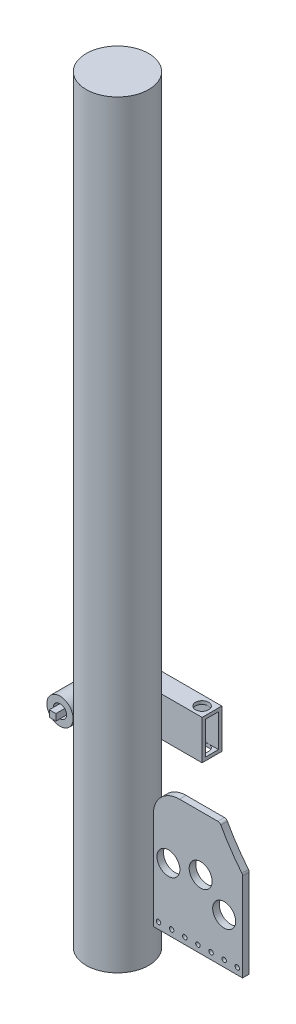
SolidWorks part; units mm, degrees
ref_plane "Front Plane" through (0, 0, 0) normal (0, 0, 1) x (1, 0, 0)
ref_plane "Top Plane" through (0, 0, 0) normal (0, 1, 0) x (1, 0, 0)
ref_plane "Right Plane" through (0, 0, 0) normal (1, 0, 0) x (0, 0, -1)
sketch "Elevation Bar" plane through (0, 0, 0) normal (0, 1, 0) x (1, 0, 0)
  circle A0 centre (0, 0) radius 30.226
  dimension "D1" = 60.452
extrude "Elevation Bar Part" add sketch "Elevation Bar" along normal blind 734.06
sketch "Pole and Drivetrain Pos" plane through (0, 0, 0) normal (0, 0, 1) x (1, 0, 0)
  line L0 (0, 0) -> (172.1794, 0) construction
  line L1 (-30.226, 0) -> (-30.226, 734.06) construction
  line L2 (-30.226, 734.06) -> (30.226, 734.06) construction
  line L3 (30.226, 734.06) -> (30.226, 0) construction
  line L4 (30.226, 0) -> (30.226, 734.06) construction
  line L5 (636.651, 41.275) -> (27.051, 41.275) construction
  line L6 (636.651, 53.975) -> (27.051, 53.975)
  line L7 (636.651, 53.975) -> (636.651, 28.575)
  line L8 (636.651, 28.575) -> (27.051, 28.575)
  line L9 (27.051, 53.975) -> (27.051, 28.575)
  line L10 (-30.226, 93.98) -> (30.226, 93.98) construction
  line L11 (33.2486, 0) -> (-33.2486, 0) construction
  line L12 (30.226, 185.42) -> (-30.226, 185.42) construction
  line L13 (30.226, 276.86) -> (-30.226, 276.86) construction
  line L14 (30.226, 368.3) -> (-30.226, 368.3) construction
  line L15 (30.226, 459.74) -> (-30.226, 459.74) construction
  line L16 (30.226, 551.18) -> (-30.226, 551.18) construction
  line L17 (30.226, 642.62) -> (-30.226, 642.62) construction
  line L18 (30.226, 73.152) -> (750.8896, 73.152) construction
  circle A0 centre (579.501, 41.275) radius 41.275 construction
  circle A1 centre (84.201, 41.275) radius 41.275 construction
  circle A2 centre (331.851, 41.275) radius 41.275 construction
  circle A3 centre (84.201, 41.275) radius 25.4
  point P24 (331.851, 41.275)
  dimension "D2" = 82.55
  dimension "D5" = 50.8
  dimension "D1" = 609.6
  dimension "D3" = 25.4
  dimension "D6" = 93.98
  dimension "D7" = 185.42
  dimension "D8" = 276.86
  dimension "D9" = 368.3
  dimension "D10" = 459.74
  dimension "D11" = 551.18
  dimension "D12" = 642.62
  dimension "D13" = 73.152
  dimension "D14" = 57.15
  dimension "D4" = 57.15
  dimension "D15" = 6.35
sketch "Driving Wheels Geo" plane through (0, 0, 0) normal (0, 0, 1) x (1, 0, 0)
  line L0 (-30.226, 182.88) -> (-30.226, 101.727) construction
  line L1 (55.626, 101.727) -> (30.226, 101.727) construction
  line L2 (-30.226, 0) -> (-30.226, 734.06) construction
  line L3 (30.226, 734.06) -> (30.226, 0) construction
  line L5 (30.226, 101.727) -> (-30.226, 101.727) construction
  line L6 (-30.226, 182.88) -> (30.226, 101.727) construction
  line L7 (31.8135, 101.727) -> (-30.226, 182.88) construction
  line L8 (30.226, 227.417) -> (203.668, 53.975) construction
  line L9 (-42.926, 195.58) -> (44.8729, 195.58) construction
  line L10 (30.226, 73.152) -> (750.8896, 73.152) construction
  line L11 (636.651, 53.975) -> (27.051, 53.975) construction
  line L14 (-42.926, 170.18) -> (44.8729, 170.18) construction
  line L15 (44.8729, 170.18) -> (44.8729, 195.58) construction
  line L16 (81.026, 28.575) -> (81.026, 257.175) construction
  line L17 (32.1729, 195.58) -> (57.5729, 195.58) construction
  line L18 (32.1729, 195.58) -> (32.1729, 170.18) construction
  line L19 (32.1729, 170.18) -> (57.5729, 170.18) construction
  line L20 (57.5729, 195.58) -> (57.5729, 170.18) construction
  line L21 (32.1729, 195.58) -> (57.5729, 170.18) construction
  line L22 (32.1729, 170.18) -> (57.5729, 195.58) construction
  line L23 (636.651, 28.575) -> (27.051, 28.575) construction
  line L24 (284.226, 257.175) -> (81.026, 257.175) construction
  line L25 (284.226, 257.175) -> (284.226, 53.975) construction
  line L26 (81.026, 257.175) -> (30.226, 257.175) construction
  circle A1 centre (55.626, 101.727) radius 25.4
  circle A3 centre (-42.926, 182.88) radius 12.7
  circle A4 centre (81.026, 104.775) radius 50.8 construction
  circle A5 centre (55.626, 101.727) radius 23.8125 construction
  circle A7 centre (284.226, 257.175) radius 203.2 construction
  point P28 (44.8729, 182.88)
  dimension "D1" = 50.8
  dimension "D2" = 1.5875
  dimension "D3" = 52.603
  dimension "D4" = 3.175
  dimension "D5" = 182.88
  dimension "D8" = 101.6
  dimension "D6" = 25.4
  dimension "D13" = 3.175
  dimension "D14" = 50.8
  dimension "D16" = 406.4
  dimension "D7" = 81.153
  dimension "D9" = 45
  dimension "D10" = 53.317
  dimension "D11" = 25.4
  dimension "D12" = 47.752
ref_plane "Plane1" through (0, 182.88, 0) normal (0, 1, 0) x (1, 0, 0)
sketch "Clamp Geo" plane through (0, 182.88, 0) normal (0, 1, 0) x (1, 0, 0)
  line L0 (-42.926, -19.8438) -> (-42.926, 50.8635) construction
  line L3 (27.051, 228.6) -> (27.051, -228.6) construction
  line L4 (50.0464, 31.8135) -> (-49.276, 31.8135)
  line L5 (50.0464, 31.8135) -> (50.0464, 50.8635)
  line L6 (50.0464, 50.8635) -> (-49.276, 50.8635)
  line L7 (-49.276, 31.8135) -> (-49.276, 50.8635)
  line L10 (-46.101, 50.8635) -> (-39.751, 50.8635)
  line L11 (-46.101, 50.8635) -> (-46.101, -19.8438)
  line L12 (-46.101, -19.8438) -> (-39.751, -19.8438)
  line L13 (-39.751, 50.8635) -> (-39.751, -19.8438)
  line L14 (-55.626, 12.7) -> (-30.226, 12.7) construction
  line L15 (-55.626, 12.7) -> (-55.626, -12.7) construction
  line L16 (-55.626, -12.7) -> (-30.226, -12.7) construction
  line L17 (-30.226, 12.7) -> (-30.226, -12.7) construction
  line L18 (-55.626, 12.7) -> (-30.226, -12.7) construction
  line L19 (-55.626, -12.7) -> (-30.226, 12.7) construction
  line L20 (0, -30.226) -> (0, 30.226) construction
  line L21 (-30.226, 0) -> (30.226, 0) construction
  line L22 (-46.101, 46.101) -> (-42.926, 46.101) construction
  line L23 (-39.751, 41.3385) -> (-46.101, 41.3385)
  line L24 (-46.101, 41.3385) -> (-46.101, 50.8635) construction
  line L25 (-39.751, 31.8135) -> (-39.751, 50.8635) construction
  line L26 (50.0464, 41.3385) -> (40.5214, 41.3385) construction
  circle A0 centre (0, 0) radius 30.226 construction
  circle A3 centre (-42.926, 46.101) radius 1.8288
  circle A5 centre (-42.926, 36.576) radius 1.8288
  circle A6 centre (40.5214, 41.3385) radius 6.35
  circle A7 centre (40.5214, 41.3385) radius 13.4704 construction
  point P14 (-42.926, 0)
  point P32 (-39.751, 41.3385)
  point P34 (-46.101, 41.3385)
  point P36 (-42.926, 41.3385)
  point P42 (50.0464, 41.3385)
  dimension "D1" = 60.452
  dimension "D4" = 1.5875
  dimension "D7" = 3.6576
  dimension "D8" = 3.175
  dimension "D10" = 12.7
  dimension "D11" = 3.175
  dimension "D2" = 457.2
  dimension "D3" = 19.05
  dimension "D5" = 6.35
  dimension "D6" = 25.4
  dimension "D9" = 99.3224
  dimension "D13" = 7.1437
sketch "Locked Setting Geo" plane through (0, 182.88, 0) normal (0, 1, 0) x (1, 0, 0)
  line L0 (30.2525, 144.301) -> (91.1428, 108.3583) construction
  line L1 (27.477, 37.9778) -> (77.9656, 123.5104)
  line L2 (27.477, 37.9778) -> (43.8821, 28.2941)
  line L3 (43.8821, 28.2941) -> (94.3707, 113.8267)
  line L4 (77.9656, 123.5104) -> (94.3707, 113.8267)
  line L5 (92.7568, 111.0925) -> (89.5289, 105.6242)
  line L6 (92.7568, 111.0925) -> (31.8664, 147.0352)
  line L7 (31.8664, 147.0352) -> (28.6385, 141.5668)
  line L8 (89.5289, 105.6242) -> (28.6385, 141.5668)
  line L9 (64.7337, 138.6948) -> (51.8221, 116.8213) construction
  line L10 (64.7337, 138.6948) -> (42.8602, 151.6064) construction
  line L11 (42.8602, 151.6064) -> (29.9486, 129.7329) construction
  line L12 (51.8221, 116.8213) -> (29.9486, 129.7329) construction
  line L13 (64.7337, 138.6948) -> (29.9486, 129.7329) construction
  line L14 (42.8602, 151.6064) -> (51.8221, 116.8213) construction
  line L17 (88.6555, 113.5135) -> (87.0416, 110.7793) construction
  line L18 (81.3263, 110.466) -> (84.5542, 115.9344)
  line L19 (84.5542, 115.9344) -> (92.7568, 111.0925) construction
  line L20 (73.1238, 115.3079) -> (89.5289, 105.6242) construction
  line L21 (35.6795, 33.1359) -> (40.5214, 41.3385) construction
  line L22 (50.0464, 50.8635) -> (-49.276, 50.8635) construction
  line L23 (-46.101, 50.8635) -> (-46.101, -19.8438) construction
  line L24 (27.051, 228.6) -> (27.051, -228.6) construction
  circle A1 centre (87.0416, 110.7793) radius 1.8288
  circle A2 centre (78.839, 115.6211) radius 1.8288
  circle A3 centre (40.5214, 41.3385) radius 6.35
  point P10 (47.3411, 134.2138)
  point P28 (81.3263, 110.466)
  point P30 (84.5542, 115.9344)
  point P32 (82.9403, 113.2002)
  point P36 (35.6795, 33.1359)
  point P40 (40.5214, 41.3385)
  point P44 (-17.1792, 28.8062)
  dimension "D6" = 3.6576
  dimension "D9" = 12.7
  dimension "D2" = 19.05
  dimension "D3" = 1.5875
  dimension "D4" = 6.35
  dimension "D5" = 25.4
  dimension "D7" = 3.175
  dimension "D8" = 99.3224
  dimension "D10" = 3.175
  dimension "D11" = 50.8635
  dimension "D12" = 67.3197
extrude "Boss-Extrude1" add sketch "Clamp Geo" along normal blind 19.05 and the other way blind 19.05 separate body contours L6 L13 L4 L5 A6 | L11 L6 L7 L4 | L13 L23 L11 L4 A5 | L23 L13 L6 L11 A3 region at (2.3187, 182.88, -41.3385) region at (-42.926, 182.88, -31.928) region at (-47.6885, 182.88, -41.3385) region at (-42.926, 182.88, -41.453)
sketch "Sketch2" plane through (-49.276, 0, 0) normal (-1, 0, 0) x (0, 0, 1)
  line L0 (-41.3385, 201.93) -> (-41.3385, 163.83) construction
  line L1 (-31.8135, 201.93) -> (-50.8635, 201.93) construction
  line L2 (-31.8135, 163.83) -> (-50.8635, 163.83) construction
  line L3 (-31.8135, 163.83) -> (-31.8135, 201.93) construction
  line L4 (-47.6885, 167.005) -> (-34.9885, 167.005)
  line L5 (-47.6885, 167.005) -> (-47.6885, 198.755)
  line L6 (-47.6885, 198.755) -> (-34.9885, 198.755)
  line L7 (-34.9885, 167.005) -> (-34.9885, 198.755)
  line L8 (-47.6885, 167.005) -> (-34.9885, 198.755) construction
  line L9 (-47.6885, 198.755) -> (-34.9885, 167.005) construction
  point P6 (-41.3385, 182.88)
  dimension "D1" = 3.175
  dimension "D2" = 3.175
extrude "Cut-Extrude2" cut sketch "Sketch2" against normal up to surface (99.3224 mm away) up to face at (50.0464, 182.88, -41.3385)
sketch "Sketch3" plane through (0, 0, -50.8635) normal (0, 0, -1) x (-1, 0, 0)
  line L2 (39.7129, 179.6669) -> (46.1391, 179.6669)
  line L3 (39.7129, 179.6669) -> (39.7129, 186.0931)
  line L4 (39.7129, 186.0931) -> (46.1391, 186.0931)
  line L5 (46.1391, 179.6669) -> (46.1391, 186.0931)
  line L6 (39.7129, 179.6669) -> (46.1391, 186.0931) construction
  line L7 (39.7129, 186.0931) -> (46.1391, 179.6669) construction
  point P0 (42.926, 182.88)
  point P1 (42.926, 182.88)
  dimension "D1" = 6.4262
extrude "Cut-Extrude3" cut sketch "Sketch3" against normal up to surface (19.05 mm away) up to face at (0.3852, 182.88, -31.8135)
extrude "Boss-Extrude2" add sketch "Clamp Geo<3>" along normal blind 3.175 and the other way blind 3.175 separate body contours L13 L4 L11 L12 | L13 L23 L11 L4 A5 | L23 L13 L6 L11 A3 region at (-42.926, 182.88, -5.9849) region at (-42.926, 182.88, -31.928) region at (-42.926, 182.88, -41.453)
sketch "Clamp Geo<3>" plane through (0, 182.88, 0) normal (0, 1, 0) x (1, 0, 0) same geometry as "Clamp Geo"
sketch "Custom Driven Flywheel" plane through (0, 0, 0) normal (0, 0, 1) x (1, 0, 0)
  circle A0 centre (-42.926, 182.88) radius 12.7 construction
  circle A1 centre (-42.926, 182.88) radius 12.7
  circle A2 centre (-42.926, 182.88) radius 6.35
  dimension "D1" = 12.7
extrude "Boss-Extrude3" add sketch "Custom Driven Flywheel" along normal mid plane 25.4 separate body
sketch "Sketch8" plane through (0, 167.005, 0) normal (0, 1, 0) x (1, 0, 0)
  line L0 (-42.926, 47.6885) -> (-42.926, 34.9885) construction
  line L1 (-49.276, 34.9885) -> (-36.576, 34.9885) construction
  line L2 (-49.276, 34.9885) -> (-49.276, 47.6885)
  line L3 (-49.276, 47.6885) -> (-36.576, 47.6885) construction
  line L4 (-36.576, 34.9885) -> (-36.576, 47.6885)
  line L5 (-36.576, 41.3385) -> (-42.926, 41.3385) construction
  line L6 (-42.926, 41.3385) -> (-49.276, 41.3385) construction
  line L7 (-43.8339, 34.9885) -> (-49.276, 34.9885)
  line L8 (-43.8339, 47.6885) -> (-49.276, 47.6885)
  line L9 (-42.0181, 34.9885) -> (-36.576, 34.9885)
  line L10 (-42.0181, 47.6885) -> (-36.576, 47.6885)
  arc A0 (-43.8339, 47.6885) -> (-42.0181, 47.6885) centre (-42.926, 46.101) ccw construction
  arc A2 (-42.0181, 34.9885) -> (-43.8339, 34.9885) centre (-42.926, 36.576) ccw construction
  arc A3 (-43.8339, 47.6885) -> (-42.0181, 47.6885) centre (-42.926, 46.101) ccw
  arc A4 (-42.0181, 34.9885) -> (-43.8339, 34.9885) centre (-42.926, 36.576) ccw
extrude "Boss-Extrude5" add sketch "Sketch8" along normal up to surface (15.875 mm away) separate body up to plane "Plane1"
sketch "Sketch10" plane through (0, 182.88, 0) normal (0, 1, 0) x (1, 0, 0)
  line L0 (-36.576, 41.3385) -> (-49.276, 41.3385) construction
  line L1 (-36.576, 34.9885) -> (-36.576, 47.6885) construction
  line L2 (-49.276, 47.6885) -> (-49.276, 34.9885) construction
  line L3 (-49.276, 34.9885) -> (-43.8339, 34.9885) construction
  line L4 (-46.1391, 34.9885) -> (-39.7129, 34.9885)
  line L5 (-46.1391, 34.9885) -> (-46.1391, 47.6885)
  line L6 (-46.1391, 47.6885) -> (-39.7129, 47.6885)
  line L7 (-39.7129, 34.9885) -> (-39.7129, 47.6885)
  line L8 (-46.1391, 34.9885) -> (-39.7129, 47.6885) construction
  line L9 (-46.1391, 47.6885) -> (-39.7129, 34.9885) construction
  point P6 (-42.926, 41.3385)
  dimension "D1" = 6.4262
extrude "Cut-Extrude5" cut sketch "Sketch10" against normal blind 6.3881
ref_plane "Plane2" through (0, 0, 210.82) normal (0, 0, 1) x (1, 0, 0)
ref_plane "Plane3" through (0, 0, 166.37) normal (0, 0, 1) x (1, 0, 0)
sketch "Sketch12" plane through (0, 0, 166.37) normal (0, 0, 1) x (1, 0, 0)
  line L0 (636.651, 41.275) -> (27.051, 41.275) construction
  line L1 (636.651, 41.275) -> (27.051, 41.275) construction
  line L2 (84.201, 41.275) -> (96.901, 41.275) construction
  line L3 (109.601, 41.275) -> (109.601, 85.2691) construction
  circle A0 centre (84.201, 41.275) radius 25.4 construction
  circle A1 centre (84.201, 41.275) radius 25.4
  circle A2 centre (55.626, 101.727) radius 21.1667
  circle A4 centre (86.8604, 107.4259) radius 10.5833
  circle A5 centre (128.651, 41.275) radius 19.05
  circle A7 centre (86.8604, 107.4259) radius 21.1667
  circle A8 centre (109.601, 85.2691) radius 10.5833
  circle A9 centre (109.601, 85.2691) radius 25.4
  circle A10 centre (84.201, 41.275) radius 3.175 construction
  circle A11 centre (96.901, 41.275) radius 3.175 construction
  circle A12 centre (109.601, 41.275) radius 3.175 construction
  circle A13 centre (122.301, 41.275) radius 3.175 construction
  circle A14 centre (135.001, 41.275) radius 3.175 construction
  circle A15 centre (147.701, 41.275) radius 3.175 construction
  circle A16 centre (160.401, 41.275) radius 3.175 construction
  circle A17 centre (173.101, 41.275) radius 3.175 construction
  circle A18 centre (185.801, 41.275) radius 3.175 construction
  circle A19 centre (198.501, 41.275) radius 3.175 construction
  point P3 (55.626, 101.727)
  dimension "D1" = 42.3333
  dimension "D2" = 21.1667
  dimension "D3" = 50.8
  dimension "D4" = 38.1
  dimension "D5" = 42.3333
  dimension "D6" = 21.1667
  dimension "D8" = 6.35
  dimension "D10" = 12.7
  dimension "D9" = 10
sketch "Sketch13" plane through (0, 0, 210.82) normal (0, 0, 1) x (1, 0, 0)
  line L0 (109.601, 72.5691) -> (109.601, 97.9691) construction
  line L2 (90.551, 72.5691) -> (90.551, 97.9691)
  line L4 (154.051, 72.5691) -> (154.051, 97.9691)
  line L5 (147.701, 85.2691) -> (147.701, 41.275) construction
  line L6 (109.601, 85.2691) -> (154.051, 85.2691) construction
  line L7 (90.551, 85.2691) -> (109.601, 85.2691) construction
  line L8 (90.551, 97.9691) -> (109.601, 97.9691)
  line L9 (90.551, 72.5691) -> (109.601, 72.5691)
  line L10 (109.601, 97.9691) -> (154.051, 97.9691)
  line L11 (154.051, 72.5691) -> (109.601, 72.5691)
  circle A0 centre (109.601, 85.2691) radius 3.175 construction
  circle A1 centre (96.901, 85.2691) radius 3.175 construction
  circle A2 centre (147.701, 85.2691) radius 3.175 construction
  point P0 (109.601, 85.2691)
  dimension "D2" = 6.35
  dimension "D3" = 6.35
  dimension "D6" = 6.35
  dimension "D1" = 25.4
  dimension "D4" = 12.7
  dimension "D5" = 6.35
ref_plane "Plane5" through (0, 0, 146.177) normal (0, 0, 1) x (1, 0, 0)
sketch "Sketch15" plane through (0, 0, 146.177) normal (0, 0, 1) x (1, 0, 0)
  line L0 (90.551, 72.5691) -> (109.601, 72.5691) construction
  line L1 (154.051, 72.5691) -> (109.601, 72.5691) construction
  line L2 (154.051, 72.5691) -> (154.051, 97.9691) construction
  line L3 (109.601, 97.9691) -> (154.051, 97.9691) construction
  line L4 (90.551, 97.9691) -> (109.601, 97.9691) construction
  line L5 (90.551, 72.5691) -> (90.551, 97.9691) construction
  line L6 (90.551, 72.5691) -> (109.601, 72.5691)
  line L7 (154.051, 72.5691) -> (109.601, 72.5691)
  line L8 (154.051, 72.5691) -> (154.051, 97.9691)
  line L9 (109.601, 97.9691) -> (154.051, 97.9691)
  line L10 (90.551, 97.9691) -> (109.601, 97.9691)
  line L11 (90.551, 72.5691) -> (90.551, 97.9691)
  line L12 (90.551, 28.575) -> (109.601, 28.575)
  line L13 (154.051, 28.575) -> (109.601, 28.575)
  line L14 (154.051, 28.575) -> (154.051, 53.975)
  line L15 (109.601, 53.975) -> (154.051, 53.975)
  line L16 (90.551, 53.975) -> (109.601, 53.975)
  line L17 (90.551, 28.575) -> (90.551, 53.975)
  line L18 (154.051, 28.575) -> (90.551, 53.975) construction
  line L19 (109.601, 53.975) -> (109.601, 28.575) construction
  line L20 (154.051, 41.275) -> (90.551, 41.275) construction
  circle A0 centre (109.601, 85.2691) radius 3.175 construction
  circle A1 centre (109.601, 85.2691) radius 3.175
  circle A2 centre (109.601, 41.275) radius 3.175 construction
  dimension "D5" = 6.35
  dimension "D1" = 68.3916
  dimension "D2" = 68.3916
  dimension "D3" = 19.05
  dimension "D4" = 25.4
ref_plane "Plane6" through (0, 53.975, 0) normal (0, 1, 0) x (1, 0, 0)
sketch "Sketch16" plane through (0, 53.975, 0) normal (0, 1, 0) x (1, 0, 0)
  line L0 (27.051, -127) -> (27.051, 127)
  line L1 (33.401, 120.65) -> (33.401, 107.95) construction
  line L2 (27.051, 127) -> (39.751, 127)
  line L3 (27.051, 127) -> (27.051, -127)
  line L4 (27.051, -127) -> (39.751, -127)
  line L5 (39.751, 127) -> (39.751, -127)
  line L6 (33.401, 120.65) -> (33.401, 127) construction
  line L7 (135.001, -166.37) -> (135.001, -127) construction
  line L8 (636.651, 0) -> (27.051, 0) construction
  line L9 (128.651, 127) -> (141.351, 127)
  line L14 (128.651, 127) -> (128.651, -127)
  line L15 (128.651, -127) -> (141.351, -127)
  line L16 (141.351, 127) -> (141.351, -127)
  line L17 (128.651, 127) -> (141.351, -127) construction
  line L18 (128.651, -127) -> (141.351, 127) construction
  line L19 (135.001, -120.65) -> (135.001, -107.95) construction
  line L20 (135.001, -127) -> (135.001, -120.65) construction
  circle A0 centre (33.401, 120.65) radius 3.175
  circle A1 centre (33.401, 107.95) radius 3.175
  circle A2 centre (33.401, 95.25) radius 3.175
  circle A3 centre (33.401, 82.55) radius 3.175
  circle A4 centre (33.401, 69.85) radius 3.175
  circle A5 centre (33.401, 57.15) radius 3.175
  circle A6 centre (33.401, 44.45) radius 3.175
  circle A7 centre (33.401, 31.75) radius 3.175
  circle A8 centre (33.401, 19.05) radius 3.175
  circle A9 centre (33.401, 6.35) radius 3.175
  circle A10 centre (33.401, -6.35) radius 3.175
  circle A11 centre (33.401, -19.05) radius 3.175
  circle A12 centre (33.401, -31.75) radius 3.175
  circle A13 centre (33.401, -44.45) radius 3.175
  circle A14 centre (33.401, -57.15) radius 3.175
  circle A15 centre (33.401, -69.85) radius 3.175
  circle A16 centre (33.401, -82.55) radius 3.175
  circle A17 centre (33.401, -95.25) radius 3.175
  circle A18 centre (33.401, -107.95) radius 3.175
  circle A19 centre (33.401, -120.65) radius 3.175
  circle A40 centre (135.001, -120.65) radius 3.175
  circle A41 centre (135.001, -107.95) radius 3.175
  circle A42 centre (135.001, -95.25) radius 3.175
  circle A43 centre (135.001, -82.55) radius 3.175
  circle A44 centre (135.001, -69.85) radius 3.175
  circle A45 centre (135.001, -57.15) radius 3.175
  circle A46 centre (135.001, -44.45) radius 3.175
  circle A47 centre (135.001, -31.75) radius 3.175
  circle A48 centre (135.001, -19.05) radius 3.175
  circle A49 centre (135.001, -6.35) radius 3.175
  circle A50 centre (135.001, 6.35) radius 3.175
  circle A51 centre (135.001, 19.05) radius 3.175
  circle A52 centre (135.001, 31.75) radius 3.175
  circle A53 centre (135.001, 44.45) radius 3.175
  circle A54 centre (135.001, 57.15) radius 3.175
  circle A55 centre (135.001, 69.85) radius 3.175
  circle A56 centre (135.001, 82.55) radius 3.175
  circle A57 centre (135.001, 95.25) radius 3.175
  circle A58 centre (135.001, 107.95) radius 3.175
  circle A59 centre (135.001, 120.65) radius 3.175
  point P3 (27.051, 0)
  point P9 (135.001, -166.37)
  point P51 (135.001, 0)
  dimension "D3" = 6.35
  dimension "D1" = 254
  dimension "D2" = 12.7
  dimension "D4" = 6.35
  dimension "D6" = 12.7
  dimension "D10" = 6.35
  dimension "D12" = 12.7
  dimension "D5" = 20
  dimension "D11" = 20
sketch "Sketch18" plane through (0, 53.975, 0) normal (0, 1, 0) x (1, 0, 0)
  line L0 (39.751, -36.5125) -> (128.651, -36.5125)
  line L1 (39.751, 127) -> (39.751, -127) construction
  line L2 (128.651, 127) -> (128.651, -127) construction
  line L3 (636.651, 0) -> (27.051, 0) construction
  line L4 (39.751, -49.2125) -> (128.651, -49.2125)
  line L5 (39.751, -36.5125) -> (39.751, -49.2125)
  line L6 (128.651, -36.5125) -> (128.651, -49.2125)
  line L7 (39.751, -42.8625) -> (128.651, -42.8625) construction
  line L8 (46.101, -42.8625) -> (58.801, -42.8625) construction
  line L9 (-403.733, 0) -> (403.733, 0) construction
  line L10 (46.101, 42.8625) -> (58.801, 42.8625) construction
  line L11 (39.751, 42.8625) -> (128.651, 42.8625) construction
  line L12 (128.651, 36.5125) -> (128.651, 49.2125)
  line L13 (39.751, 36.5125) -> (39.751, 49.2125)
  line L14 (39.751, 49.2125) -> (128.651, 49.2125)
  line L15 (39.751, 36.5125) -> (128.651, 36.5125)
  circle A0 centre (46.101, -42.8625) radius 3.175
  circle A1 centre (58.801, -42.8625) radius 3.175
  circle A2 centre (71.501, -42.8625) radius 3.175
  circle A3 centre (84.201, -42.8625) radius 3.175
  circle A4 centre (96.901, -42.8625) radius 3.175
  circle A5 centre (109.601, -42.8625) radius 3.175
  circle A6 centre (122.301, -42.8625) radius 3.175
  circle A7 centre (122.301, 42.8625) radius 3.175
  circle A8 centre (109.601, 42.8625) radius 3.175
  circle A9 centre (96.901, 42.8625) radius 3.175
  circle A10 centre (84.201, 42.8625) radius 3.175
  circle A11 centre (71.501, 42.8625) radius 3.175
  circle A12 centre (58.801, 42.8625) radius 3.175
  circle A13 centre (46.101, 42.8625) radius 3.175
  dimension "D4" = 6.35
  dimension "D1" = 36.5125
  dimension "D2" = 12.7
  dimension "D3" = 6.35
  dimension "D6" = 12.7
  dimension "D5" = 7
sketch "Sketch17" plane through (0, 0, 0) normal (0, 0, 1) x (1, 0, 0)
  line L0 (41.021, 53.975) -> (41.021, 135.255)
  line L2 (127.381, 126.8514) -> (127.381, 53.975)
  line L6 (128.651, 53.975) -> (141.351, 53.975) construction
  line L9 (636.651, 53.975) -> (27.051, 53.975) construction
  line L10 (41.021, 53.975) -> (41.021, 41.275)
  line L11 (41.021, 41.275) -> (127.381, 41.275)
  line L13 (127.381, 53.975) -> (127.381, 41.275)
  line L14 (55.626, 101.727) -> (55.626, 41.275) construction
  line L16 (66.421, 160.655) -> (103.5286, 160.655)
  line L17 (50.0464, 163.83) -> (-49.276, 163.83) construction
  circle A0 centre (55.626, 101.727) radius 11.1125
  circle A1 centre (86.8604, 107.4259) radius 11.1125
  circle A2 centre (109.601, 85.2691) radius 11.1125
  circle A6 centre (284.226, 257.175) radius 203.2 construction
  arc A7 (106.3086, 159.0138) -> (126.6678, 128.8564) centre (284.226, 257.175) ccw
  arc A8 (41.021, 135.255) -> (66.421, 160.655) centre (66.421, 135.255) cw
  arc A9 (127.381, 126.8514) -> (126.6678, 128.8564) centre (124.206, 126.8514) ccw
  arc A10 (103.5286, 160.655) -> (106.3086, 159.0138) centre (103.5286, 157.48) cw
  point P14 (41.021, 182.88)
  point P15 (41.021, 160.6434)
  point P25 (127.381, 127.9857)
  dimension "D1" = 22.225
  dimension "D6" = 25.4
  dimension "D7" = 3.175
  dimension "D4" = 12.7
  dimension "D5" = 13.97
  dimension "D3" = 13.97
  dimension "D2" = 3.175
sketch "Sketch19" plane through (0, 0, 0) normal (0, 0, 1) x (1, 0, 0)
  line L0 (46.101, 47.625) -> (122.301, 47.625) construction
  line L1 (46.101, 41.275) -> (46.101, 53.975) construction
  line L2 (636.651, 41.275) -> (27.051, 41.275) construction
  line L3 (636.651, 53.975) -> (27.051, 53.975) construction
  line L4 (46.101, 47.625) -> (58.801, 47.625) construction
  circle A0 centre (46.101, 47.625) radius 2.1527
  circle A1 centre (58.801, 47.625) radius 2.1527
  circle A2 centre (71.501, 47.625) radius 2.1527
  circle A3 centre (84.201, 47.625) radius 2.1527
  circle A4 centre (96.901, 47.625) radius 2.1527
  circle A5 centre (109.601, 47.625) radius 2.1527
  circle A6 centre (122.301, 47.625) radius 2.1527
  point P5 (121.8147, 47.625)
  dimension "D2" = 4.3053
  dimension "D1" = 6.35
  dimension "D4" = 12.7
  dimension "D3" = 7
extrude "Boss-Extrude6" add sketch "Sketch17" along normal blind 6.35 separate body
extrude "Cut-Extrude7" cut sketch "Sketch19" along normal blind 6.35
sketch "Sketch20" [suppressed] plane through (0, 0, 6.35) normal (0, 0, 1) x (1, 0, 0)
  line L0 (41.021, 56.515) -> (127.381, 56.515)
  line L1 (41.021, 135.255) -> (41.021, 41.275) construction
  line L2 (127.381, 41.275) -> (127.381, 126.8514) construction
  line L10 (41.021, 135.255) -> (41.021, 41.275)
  line L11 (41.021, 41.275) -> (127.381, 41.275)
  line L12 (127.381, 41.275) -> (127.381, 126.8514)
  line L13 (103.5286, 160.655) -> (66.421, 160.655)
  line L14 (41.021, 135.255) -> (41.021, 41.275) construction
  line L19 (41.021, 124.8884) -> (127.381, 124.8884)
  line L20 (46.101, 124.8884) -> (54.991, 140.2864)
  line L21 (54.991, 140.2864) -> (63.881, 124.8884)
  line L22 (63.881, 124.8884) -> (72.771, 140.2864)
  line L23 (72.771, 140.2864) -> (81.661, 124.8884)
  line L25 (54.991, 140.2864) -> (72.771, 140.2864)
  line L26 (72.771, 140.2864) -> (108.331, 140.2864)
  line L27 (81.661, 124.8884) -> (90.551, 140.2864)
  line L28 (90.551, 140.2864) -> (99.441, 124.8884)
  line L29 (99.441, 124.8884) -> (108.331, 140.2864)
  line L30 (108.331, 140.2864) -> (117.221, 124.8884)
  line L31 (54.991, 140.2864) -> (63.881, 155.6843)
  line L32 (63.881, 155.6843) -> (72.771, 140.2864)
  line L33 (46.101, 124.8884) -> (46.101, 140.2864)
  line L34 (46.101, 140.2864) -> (54.991, 140.2864)
  line L35 (72.771, 140.2864) -> (81.661, 155.6843)
  line L36 (63.881, 155.6843) -> (61.8536, 155.6843)
  line L37 (81.661, 155.6843) -> (90.551, 140.2864)
  line L38 (90.551, 140.2864) -> (99.441, 155.6843)
  line L39 (99.441, 155.6843) -> (108.331, 140.2864)
  line L40 (63.881, 155.6843) -> (99.441, 155.6843)
  line L41 (117.221, 124.8884) -> (108.331, 109.4905)
  line L42 (108.331, 109.4905) -> (99.441, 124.8884)
  line L43 (117.221, 124.8884) -> (117.221, 109.4905)
  line L44 (117.221, 109.4905) -> (108.331, 109.4905)
  line L45 (117.221, 109.4905) -> (117.221, 100.9813)
  line L46 (117.221, 100.9813) -> (108.331, 109.4905)
  line L47 (46.101, 56.515) -> (54.991, 71.9129)
  line L48 (54.991, 71.9129) -> (63.881, 56.515)
  line L49 (63.881, 56.515) -> (72.771, 71.9129)
  line L50 (72.771, 71.9129) -> (81.661, 56.515)
  line L51 (81.661, 56.515) -> (90.551, 71.9129)
  line L52 (90.551, 71.9129) -> (99.441, 56.515)
  line L53 (54.991, 71.9129) -> (72.771, 71.9129)
  line L54 (90.551, 71.9129) -> (72.771, 71.9129)
  line L55 (46.101, 56.515) -> (46.101, 71.9129)
  line L56 (46.101, 71.9129) -> (54.991, 71.9129)
  line L57 (46.101, 71.9129) -> (46.101, 87.091)
  line L58 (46.3026, 86.9618) -> (54.991, 71.9129)
  line L59 (81.661, 87.3109) -> (65.4806, 87.3109)
  line L60 (81.661, 87.3109) -> (90.551, 71.9129)
  line L61 (72.771, 71.9129) -> (81.661, 87.3109)
  line L62 (64.3061, 86.5746) -> (72.771, 71.9129)
  line L63 (54.991, 71.9129) -> (63.0894, 85.9398)
  line L65 (125.5178, 67.8066) -> (105.9602, 67.8066)
  line L66 (99.441, 56.515) -> (105.9602, 67.8066)
  line L67 (112.4794, 56.515) -> (105.9602, 67.8066)
  line L68 (112.4794, 56.515) -> (118.9986, 67.8066)
  line L69 (118.9986, 67.8066) -> (125.5178, 56.515)
  line L70 (125.5178, 56.515) -> (125.5178, 67.8066)
  line L71 (105.9602, 67.8066) -> (92.9218, 67.8066)
  circle A0 centre (46.101, 47.625) radius 2.1526 construction
  arc A2 (46.101, 140.2864) -> (61.8536, 155.6843) centre (66.421, 135.255) cw
  circle A4 centre (86.8604, 107.4259) radius 17.4625 construction
  arc A5 (127.381, 126.8514) -> (126.6678, 128.8564) centre (124.206, 126.8514) ccw
  arc A6 (106.3086, 159.0138) -> (126.6678, 128.8564) centre (284.226, 257.175) ccw
  arc A7 (106.3086, 159.0138) -> (103.5286, 160.655) centre (103.5286, 157.48) ccw
  arc A8 (66.421, 160.655) -> (41.021, 135.255) centre (66.421, 135.255) ccw
  arc A12 (66.421, 160.655) -> (41.021, 135.255) centre (66.421, 135.255) ccw construction
  circle A13 centre (86.8604, 107.4259) radius 11.1125 construction
  circle A14 centre (109.601, 85.2691) radius 17.4625 construction
  circle A15 centre (109.601, 85.2691) radius 11.1125 construction
  circle A16 centre (55.626, 101.727) radius 17.4625 construction
  circle A17 centre (55.626, 101.727) radius 11.1125 construction
  arc A18 (46.101, 87.091) -> (65.4806, 87.3109) centre (55.626, 101.727) ccw
  point P73 (125.5178, 124.8884)
  point P74 (127.381, 124.8884)
  dimension "D4" = 5.08
  dimension "D3" = 6.35
  dimension "D7" = 6.35
  dimension "D8" = 6.35
  dimension "D1" = 8.89
  dimension "D5" = 60
  dimension "D6" = 17.78
  dimension "D9" = 60
  dimension "D10" = 5.08
  dimension "D11" = 60
  dimension "D12" = 60
  dimension "D13" = 60
  dimension "D14" = 60
  dimension "D2" = 0
sketch "Sketch21" [suppressed] plane through (0, 0, 6.35) normal (0, 0, 1) x (1, 0, 0)
  line L0 (117.221, 124.8884) -> (117.221, 109.4905) construction
  line L1 (117.221, 109.4905) -> (108.331, 109.4905) construction
  line L2 (117.221, 109.4905) -> (117.221, 100.9813) construction
  line L3 (117.221, 100.9813) -> (108.331, 109.4905) construction
  line L4 (72.771, 140.2864) -> (81.661, 124.8884) construction
  line L5 (81.661, 124.8884) -> (90.551, 140.2864) construction
  line L6 (90.551, 140.2864) -> (99.441, 124.8884) construction
  line L7 (72.771, 140.2864) -> (81.661, 155.6843) construction
  line L8 (81.661, 155.6843) -> (90.551, 140.2864) construction
  line L9 (90.551, 140.2864) -> (99.441, 155.6843) construction
  line L10 (72.771, 140.2864) -> (108.331, 140.2864) construction
  line L11 (99.441, 124.8884) -> (108.331, 140.2864) construction
  line L12 (108.331, 140.2864) -> (117.221, 124.8884) construction
  line L13 (99.441, 155.6843) -> (108.331, 140.2864) construction
  line L14 (41.021, 56.515) -> (127.381, 56.515) construction
  line L15 (108.331, 109.4905) -> (99.441, 124.8884) construction
  line L16 (46.101, 124.8884) -> (54.991, 140.2864) construction
  line L17 (46.101, 124.8884) -> (46.101, 140.2864) construction
  line L18 (54.991, 140.2864) -> (63.881, 124.8884) construction
  line L19 (63.881, 124.8884) -> (72.771, 140.2864) construction
  line L20 (54.991, 140.2864) -> (72.771, 140.2864) construction
  line L21 (54.991, 140.2864) -> (63.881, 155.6843) construction
  line L22 (46.101, 140.2864) -> (54.991, 140.2864) construction
  line L23 (41.021, 124.8884) -> (127.381, 124.8884) construction
  line L24 (117.221, 124.8884) -> (108.331, 109.4905) construction
  line L25 (63.881, 155.6843) -> (99.441, 155.6843) construction
  line L26 (63.881, 155.6843) -> (61.8536, 155.6843) construction
  line L27 (63.881, 155.6843) -> (72.771, 140.2864) construction
  line L28 (54.991, 71.9129) -> (63.0894, 85.9398) construction
  line L29 (46.3026, 86.9618) -> (54.991, 71.9129) construction
  line L30 (72.771, 71.9129) -> (81.661, 56.515) construction
  line L31 (81.661, 56.515) -> (90.551, 71.9129) construction
  line L32 (90.551, 71.9129) -> (99.441, 56.515) construction
  line L33 (99.441, 56.515) -> (105.9602, 67.8066) construction
  line L34 (90.551, 71.9129) -> (72.771, 71.9129) construction
  line L35 (81.661, 87.3109) -> (90.551, 71.9129) construction
  line L36 (54.991, 71.9129) -> (63.881, 56.515) construction
  line L37 (63.881, 56.515) -> (72.771, 71.9129) construction
  line L38 (54.991, 71.9129) -> (72.771, 71.9129) construction
  line L39 (72.771, 71.9129) -> (81.661, 87.3109) construction
  line L40 (64.3061, 86.5746) -> (72.771, 71.9129) construction
  line L41 (46.101, 56.515) -> (54.991, 71.9129) construction
  line L42 (46.101, 56.515) -> (46.101, 71.9129) construction
  line L43 (46.101, 71.9129) -> (54.991, 71.9129) construction
  line L44 (105.9602, 67.8066) -> (92.9218, 67.8066) construction
  line L45 (46.101, 71.9129) -> (46.101, 87.091) construction
  line L46 (81.661, 87.3109) -> (65.4806, 87.3109) construction
  line L47 (125.5178, 67.8066) -> (105.9602, 67.8066) construction
  line L48 (125.5178, 56.515) -> (125.5178, 67.8066) construction
  line L49 (118.9986, 67.8066) -> (125.5178, 56.515) construction
  line L50 (112.4794, 56.515) -> (118.9986, 67.8066) construction
  line L51 (112.4794, 56.515) -> (105.9602, 67.8066) construction
  line L52 (117.221, 124.8884) -> (117.221, 109.4905)
  line L53 (117.221, 109.4905) -> (108.331, 109.4905)
  line L54 (117.221, 109.4905) -> (117.221, 100.9813)
  line L55 (117.221, 100.9813) -> (108.331, 109.4905)
  line L56 (72.771, 140.2864) -> (81.661, 124.8884)
  line L57 (81.661, 124.8884) -> (90.551, 140.2864)
  line L58 (90.551, 140.2864) -> (99.441, 124.8884)
  line L59 (72.771, 140.2864) -> (81.661, 155.6843)
  line L60 (81.661, 155.6843) -> (90.551, 140.2864)
  line L61 (90.551, 140.2864) -> (99.441, 155.6843)
  line L62 (72.771, 140.2864) -> (108.331, 140.2864)
  line L63 (99.441, 124.8884) -> (108.331, 140.2864)
  line L64 (108.331, 140.2864) -> (117.221, 124.8884)
  line L65 (99.441, 155.6843) -> (108.331, 140.2864)
  line L66 (41.021, 56.515) -> (127.381, 56.515)
  line L67 (108.331, 109.4905) -> (99.441, 124.8884)
  line L68 (46.101, 124.8884) -> (54.991, 140.2864)
  line L69 (46.101, 124.8884) -> (46.101, 140.2864)
  line L70 (54.991, 140.2864) -> (63.881, 124.8884)
  line L71 (63.881, 124.8884) -> (72.771, 140.2864)
  line L72 (54.991, 140.2864) -> (72.771, 140.2864)
  line L73 (54.991, 140.2864) -> (63.881, 155.6843)
  line L74 (46.101, 140.2864) -> (54.991, 140.2864)
  line L75 (41.021, 124.8884) -> (127.381, 124.8884)
  line L76 (117.221, 124.8884) -> (108.331, 109.4905)
  line L77 (63.881, 155.6843) -> (99.441, 155.6843)
  line L78 (63.881, 155.6843) -> (61.8536, 155.6843)
  line L79 (63.881, 155.6843) -> (72.771, 140.2864)
  line L80 (54.991, 71.9129) -> (63.0894, 85.9398)
  line L81 (46.3026, 86.9618) -> (54.991, 71.9129)
  line L82 (72.771, 71.9129) -> (81.661, 56.515)
  line L83 (81.661, 56.515) -> (90.551, 71.9129)
  line L84 (90.551, 71.9129) -> (99.441, 56.515)
  line L85 (99.441, 56.515) -> (105.9602, 67.8066)
  line L86 (90.551, 71.9129) -> (72.771, 71.9129)
  line L87 (81.661, 87.3109) -> (90.551, 71.9129)
  line L88 (54.991, 71.9129) -> (63.881, 56.515)
  line L89 (63.881, 56.515) -> (72.771, 71.9129)
  line L90 (54.991, 71.9129) -> (72.771, 71.9129)
  line L91 (72.771, 71.9129) -> (81.661, 87.3109)
  line L92 (64.3061, 86.5746) -> (72.771, 71.9129)
  line L93 (46.101, 56.515) -> (54.991, 71.9129)
  line L94 (46.101, 56.515) -> (46.101, 71.9129)
  line L95 (46.101, 71.9129) -> (54.991, 71.9129)
  line L96 (105.9602, 67.8066) -> (92.9218, 67.8066)
  line L97 (46.101, 71.9129) -> (46.101, 87.091)
  line L98 (81.661, 87.3109) -> (65.4806, 87.3109)
  line L99 (125.5178, 67.8066) -> (105.9602, 67.8066)
  line L100 (125.5178, 56.515) -> (125.5178, 67.8066)
  line L101 (118.9986, 67.8066) -> (125.5178, 56.515)
  line L102 (112.4794, 56.515) -> (118.9986, 67.8066)
  line L103 (112.4794, 56.515) -> (105.9602, 67.8066)
  arc A0 (61.8536, 155.6843) -> (46.101, 140.2864) centre (66.421, 135.255) ccw construction
  arc A1 (46.101, 87.091) -> (65.4806, 87.3109) centre (55.626, 101.727) ccw construction
  arc A2 (61.8536, 155.6843) -> (46.101, 140.2864) centre (66.421, 135.255) ccw
  arc A3 (46.101, 87.091) -> (65.4806, 87.3109) centre (55.626, 101.727) ccw
equation "\"D4@Pole and Drivetrain Pos\"=\"D14@Pole and Drivetrain Pos\""
equation "\"D5@Sketch17\"=\"D3@Sketch17\""
